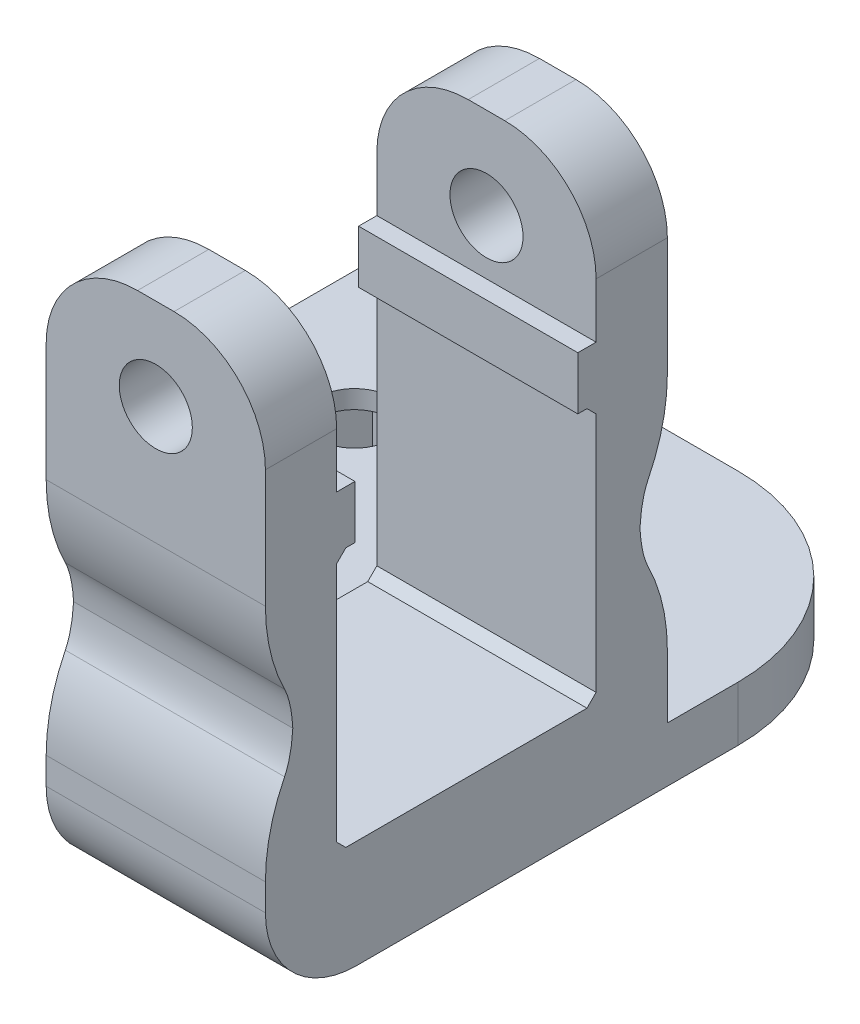
SolidWorks part; units mm, degrees
ref_plane "Plan de face" through (0, 0, 0) normal (0, 0, 1) x (1, 0, 0)
ref_plane "Plan de dessus" through (0, 0, 0) normal (0, 1, 0) x (1, 0, 0)
ref_plane "Plan de droite" through (0, 0, 0) normal (1, 0, 0) x (0, 0, -1)
sketch "Esquisse1" plane through (0, 0, 0) normal (0, 1, 0) x (1, 0, 0)
  line L1 (0, 0) -> (30, 0)
  line L2 (0, 0) -> (0, 40)
  line L3 (0, 40) -> (30, 40)
  line L4 (30, 0) -> (30, 40)
  dimension "D1" = 40
  dimension "D2" = 30
extrude "Boss.-Extru.1" add sketch "Esquisse1" along normal blind 3
sketch "Esquisse8" plane through (0, 3, 0) normal (0, 1, 0) x (1, 0, 0)
  line L1 (13, 9.625) -> (13, 13.125) construction
  line L2 (13, 9.625) -> (13, 0) construction
  line L3 (30, 0) -> (30, 40) construction
  line L4 (13, 9.625) -> (30, 9.625)
  line L5 (13, 9.625) -> (13, 13.125)
  line L6 (13, 13.125) -> (30, 13.125)
  line L7 (30, 9.625) -> (30, 13.125)
  line L8 (0, 0) -> (30, 0) construction
  line L9 (13, 9.625) -> (0, 9.625) construction
  line L10 (13, 13.125) -> (13, 40) construction
  line L11 (30, 40) -> (0, 40) construction
  dimension "D1" = 3.5
  dimension "D2" = 17
extrude "Boss.-Extru.2" add sketch "Esquisse8" along normal blind 20
sketch "Esquisse11" plane through (13, 0, 0) normal (-1, 0, 0) x (0, 0, 1)
  line L1 (-13.125, 3) -> (-9.625, 3)
  line L2 (-13.125, 3) -> (-13.125, 23)
  line L3 (-13.125, 23) -> (-9.625, 23)
  line L4 (-9.625, 3) -> (-9.625, 23)
  dimension "D1" = 20
  dimension "D2" = 3.5
extrude "Enlèv. mat.-Extru.9" cut sketch "Esquisse11" against normal blind 5
sketch "Esquisse19" plane through (0, 0, -9.625) normal (0, 0, 1) x (1, 0, 0)
  line L1 (18, 3) -> (30, 3)
  line L2 (18, 3) -> (18, 23)
  line L3 (18, 23) -> (30, 23)
  line L4 (30, 3) -> (30, 23)
  dimension "D1" = 20
  dimension "D2" = 12
extrude "Boss.-Extru.6" add sketch "Esquisse19" along normal blind 16.5
sketch "Esquisse20" plane through (18, 0, 0) normal (-1, 0, 0) x (0, 0, 1)
  line L1 (6.875, 23) -> (-13.125, 23) construction
  line L3 (-3.125, 23) -> (-3.125, 20.1) construction
  line L4 (-13.125, 13) -> (-10.225, 13) construction
  line L5 (-13.125, 23) -> (-13.125, 3) construction
  line L6 (6.875, 13) -> (3.975, 13) construction
  line L7 (6.875, 23) -> (6.875, 3) construction
  line L8 (-10.225, 20.1) -> (3.975, 20.1)
  line L9 (-10.225, 20.1) -> (-10.225, 5.9)
  line L10 (-10.225, 5.9) -> (3.975, 5.9)
  line L11 (3.975, 20.1) -> (3.975, 5.9)
  dimension "D1" = 14.2
extrude "Enlèv. mat.-Extru.11" cut sketch "Esquisse20" against normal through all
sketch "Esquisse22" plane through (0, 0, -10.225) normal (0, 0, 1) x (1, 0, 0)
  line L1 (30, 5.9) -> (18, 5.9)
  line L2 (30, 5.9) -> (30, 20.1)
  line L3 (30, 20.1) -> (18, 20.1)
  line L4 (18, 5.9) -> (18, 20.1)
  dimension "D1" = 14.2
  dimension "D2" = 12
sketch "Esquisse29" plane through (0, 0, 6.875) normal (0, 0, 1) x (1, 0, 0)
  line L1 (18, 3) -> (30, 3)
  line L2 (18, 3) -> (18, 0)
  line L3 (18, 0) -> (30, 0)
  line L4 (30, 3) -> (30, 0)
  dimension "D1" = 3
  dimension "D2" = 12
extrude "Boss.-Extru.9" add sketch "Esquisse29" against normal blind 17
sketch "Esquisse30" plane through (0, 0, 6.875) normal (0, 0, 1) x (1, 0, 0)
  line L1 (18, 0) -> (30, 0)
  line L2 (18, 0) -> (18, 23)
  line L3 (18, 23) -> (30, 23)
  line L4 (30, 0) -> (30, 23)
  dimension "D1" = 23
  dimension "D2" = 12
extrude "Boss.-Extru.10" add sketch "Esquisse30" along normal blind 1
sketch "Esquisse31" plane through (0, 0, -13.125) normal (0, 0, -1) x (-1, 0, 0)
  line L1 (-30, 3) -> (-18, 3)
  line L2 (-30, 3) -> (-30, 23)
  line L3 (-30, 23) -> (-18, 23)
  line L4 (-18, 3) -> (-18, 23)
  dimension "D1" = 20
  dimension "D2" = 12
extrude "Boss.-Extru.11" add sketch "Esquisse31" along normal blind 1
sketch "Esquisse32" plane through (18, 0, 0) normal (-1, 0, 0) x (0, 0, 1)
  line L0 (-10.225, 20.1) -> (-10.225, 23) construction
  line L1 (7.875, 23) -> (-14.125, 23) construction
  line L2 (-10.225, 23) -> (-9.225, 23) construction
  line L3 (-9.225, 23) -> (-9.225, 20.1) construction
  line L4 (3.975, 20.1) -> (-10.225, 20.1) construction
  line L5 (3.975, 20.1) -> (2.975, 20.1) construction
  line L6 (2.975, 20.1) -> (2.975, 23) construction
  line L8 (-9.225, 20.1) -> (2.975, 20.1)
  line L9 (-9.225, 20.1) -> (-9.225, 23)
  line L10 (-9.225, 23) -> (2.975, 23)
  line L11 (2.975, 20.1) -> (2.975, 23)
  dimension "D1" = 2.9
  dimension "D2" = 12.2
extrude "Enlèv. mat.-Extru.12" cut sketch "Esquisse32" against normal through all
sketch "Esquisse33" plane through (0, 23, 0) normal (0, 1, 0) x (1, 0, 0)
  line L1 (18, 14.125) -> (30, 14.125)
  line L2 (18, 14.125) -> (18, 10.225)
  line L3 (18, 10.225) -> (30, 10.225)
  line L4 (30, 14.125) -> (30, 10.225)
  line L5 (30, 9.225) -> (30, 14.125) construction
  line L7 (18, -7.875) -> (30, -7.875)
  line L8 (18, -7.875) -> (18, -3.975)
  line L9 (18, -3.975) -> (30, -3.975)
  line L10 (30, -7.875) -> (30, -3.975)
  line L11 (30, -7.875) -> (30, -2.975) construction
  dimension "D1" = 3.9
  dimension "D2" = 12
  dimension "D3" = 3.9
  dimension "D4" = 12
extrude "Boss.-Extru.12" add sketch "Esquisse33" along normal blind 8
fillet "Congé6" radius 5 4 edges at (30, 31, -12.175) (30, 31, 5.925) (18, 31, 5.925) (18, 31, -12.175)
sketch "Esquisse36" plane through (0, 0, -10.225) normal (0, 0, 1) x (1, 0, 0)
  line L0 (24, 23) -> (24, 26) construction
  line L1 (18, 23) -> (30, 23) construction
  circle A0 centre (24, 26) radius 2
extrude "Enlèv. mat.-Extru.14" cut sketch "Esquisse36" against normal through all both and the other way through all
chamfer "Chanfrein1" distance 0.5 angle 45 4 edges at (24, 20.1, 3.975) (24, 5.9, 3.975) (24, 20.1, -10.225) (24, 5.9, -10.225)
fillet "Congé7" radius 5 1 edges at (24, 0, 7.875)
sketch "Esquisse37" plane through (18, 0, 0) normal (-1, 0, 0) x (0, 0, 1)
  line L0 (-3.125, 5.9) -> (-3.125, 25.9041) construction
  line L1 (-9.725, 5.9) -> (3.475, 5.9) construction
  line L2 (3.975, 13) -> (7.875, 13) construction
  line L3 (3.975, 6.4) -> (3.975, 19.6) construction
  line L4 (7.875, 26) -> (7.875, 5) construction
  line L5 (-10.225, 13) -> (-14.125, 13) construction
  line L6 (-10.225, 5.9) -> (-10.225, 20.1) construction
  line L7 (-14.125, 3) -> (-14.125, 26) construction
  line L8 (-14.125, 13) -> (-14.125, 16) construction
  line L9 (-14.125, 13) -> (-14.125, 10) construction
  line L10 (-14.125, 13) -> (-12.625, 13) construction
  line L11 (-14.125, 16) -> (-14.125, 10)
  line L12 (7.875, 13) -> (6.375, 13) construction
  line L13 (7.875, 13) -> (7.875, 10) construction
  line L14 (7.875, 13) -> (7.875, 16) construction
  line L15 (7.875, 16) -> (7.875, 10)
  spline S0 degree 2 poles (-14.125, 16) (-12.7806, 15.6554) (-12.625, 13) knots 0 0 0 1 1 1
  spline S1 degree 2 poles (-14.125, 10) (-12.7806, 10.3446) (-12.625, 13) knots 0 0 0 1 1 1
  spline S2 degree 2 poles (7.875, 10) (6.5306, 10.3446) (6.375, 13) knots 0 0 0 1 1 1
  spline S3 degree 2 poles (7.875, 16) (6.5306, 15.6554) (6.375, 13) knots 0 0 0 1 1 1
extrude "Enlèv. mat.-Extru.15" cut sketch "Esquisse37" against normal through all
fillet "Congé8" radius 10 2 edges at (24, 10, 7.875) (24, 16, 7.875)
fillet "Congé9" radius 10 2 edges at (24, 16, -14.125) (24, 10, -14.125)
sketch "Esquisse38" plane through (0, 0, 0) normal (0, -1, 0) x (1, 0, 0)
  line L0 (0, -20) -> (7, -20) construction
  line L1 (0, -40) -> (0, 0) construction
  line L3 (0, -20) -> (7, -20) construction
  line L4 (7, -20) -> (7, -37.5) construction
  line L5 (7, -20) -> (7, -2.5) construction
  line L8 (0, -20) -> (7, -20) construction
  circle A3 centre (7, -20) radius 2
sketch "Esquisse39" plane through (0, 0, -40) normal (0, 0, -1) x (-1, 0, 0)
  line L1 (0, 0) -> (-30, 0)
  line L2 (0, 0) -> (0, 3)
  line L3 (0, 3) -> (-30, 3)
  line L4 (-30, 0) -> (-30, 3)
  line L5 (-30, 3) -> (-30, 0) construction
  dimension "D1" = 3
  dimension "D2" = 30
extrude "Boss.-Extru.13" add sketch "Esquisse39" along normal blind 2
sketch "Esquisse40" plane through (0, 0, 0) normal (0, 0, 1) x (1, 0, 0)
  line L1 (18, 0) -> (0, 0)
  line L2 (18, 0) -> (18, 3)
  line L3 (18, 3) -> (0, 3)
  line L4 (0, 0) -> (0, 3)
  dimension "D1" = 3
  dimension "D2" = 18
extrude "Boss.-Extru.14" add sketch "Esquisse40" along normal blind 2
extrude "Enlèv. mat.-Extru.16" cut sketch "Esquisse38" against normal through all
sketch "Esquisse41" plane through (0, 0, 0) normal (0, -1, 0) x (1, 0, 0)
  line L0 (7, -20) -> (2, -20) construction
  line L1 (7, -20) -> (7, -26) construction
  line L3 (2, -26) -> (12, -26)
  line L4 (2, -26) -> (2, -14)
  line L5 (2, -14) -> (12, -14)
  line L6 (12, -26) -> (12, -14)
  line L7 (0, -42) -> (0, 2) construction
  line L8 (0, -26) -> (0, -28) construction
  line L10 (0, -28) -> (14, -28)
  line L11 (0, -28) -> (0, -12)
  line L12 (0, -12) -> (14, -12)
  line L13 (14, -28) -> (14, -12)
  dimension "D1" = 12
  dimension "D2" = 10
  dimension "D3" = 16
  dimension "D4" = 14
extrude "Boss.-Extru.15" add sketch "Esquisse41" along normal blind 9
sketch "Esquisse42" plane through (0, 0, 0) normal (0, -1, 0) x (1, 0, 0)
  line L1 (12, -26) -> (2, -26)
  line L2 (12, -26) -> (12, -14)
  line L3 (12, -14) -> (2, -14)
  line L4 (2, -26) -> (2, -14)
  dimension "D1" = 12
  dimension "D2" = 10
extrude "Enlèv. mat.-Extru.17" cut sketch "Esquisse42" against normal blind 2
sketch "Esquisse43" plane through (0, 0, 0) normal (0, -1, 0) x (1, 0, 0)
  line L1 (0, -28) -> (30, -28)
  line L2 (0, -28) -> (0, -42)
  line L3 (0, -42) -> (30, -42)
  line L4 (30, -28) -> (30, -42)
  line L5 (0, -12) -> (15, 2) construction
  line L6 (0, 2) -> (18, 2) construction
  line L7 (0, -12) -> (0, 2)
  line L8 (0, 2) -> (15, 2)
  line L9 (15, 2) -> (0, -12)
  dimension "D1" = 14
  dimension "D2" = 30
extrude "Enlèv. mat.-Extru.19" cut sketch "Esquisse43" against normal blind 3
fillet "Congé10" radius 10 1 edges at (30, 1.5, -28)
sketch "Esquisse44" plane through (0, 0, 0) normal (0, -1, 0) x (1, 0, 0)
  line L1 (14, -12) -> (20, -12)
  line L2 (14, -12) -> (14, -28)
  line L3 (14, -28) -> (20, -28)
  line L4 (20, -12) -> (20, -28)
  dimension "D1" = 16
  dimension "D2" = 6
extrude "Boss.-Extru.16" add sketch "Esquisse44" along normal blind 9
chamfer "Chanfrein2" distance 7 angle 45 1 edges at (20, -9, -20)
fillet "Congé11" radius 10 1 edges at (20, -2, -20)
sketch "Esquisse46" plane through (0, -9, 0) normal (0, -1, 0) x (1, 0, 0)
  line L0 (12, -14) -> (12.1, -14) construction
  line L1 (12.1, -14) -> (12.1, -13.9) construction
  line L2 (2, -26) -> (12.1, -26.1) construction
  line L3 (12.1, -26.1) -> (1.9, -26.1) construction
  line L5 (1.9, -26.1) -> (12.1, -26.1)
  line L6 (1.9, -26.1) -> (1.9, -13.9)
  line L7 (1.9, -13.9) -> (12.1, -13.9)
  line L8 (12.1, -26.1) -> (12.1, -13.9)
  dimension "D1" = 12.2
  dimension "D2" = 10.2
extrude "Enlèv. mat.-Extru.20" cut sketch "Esquisse46" against normal blind 11
